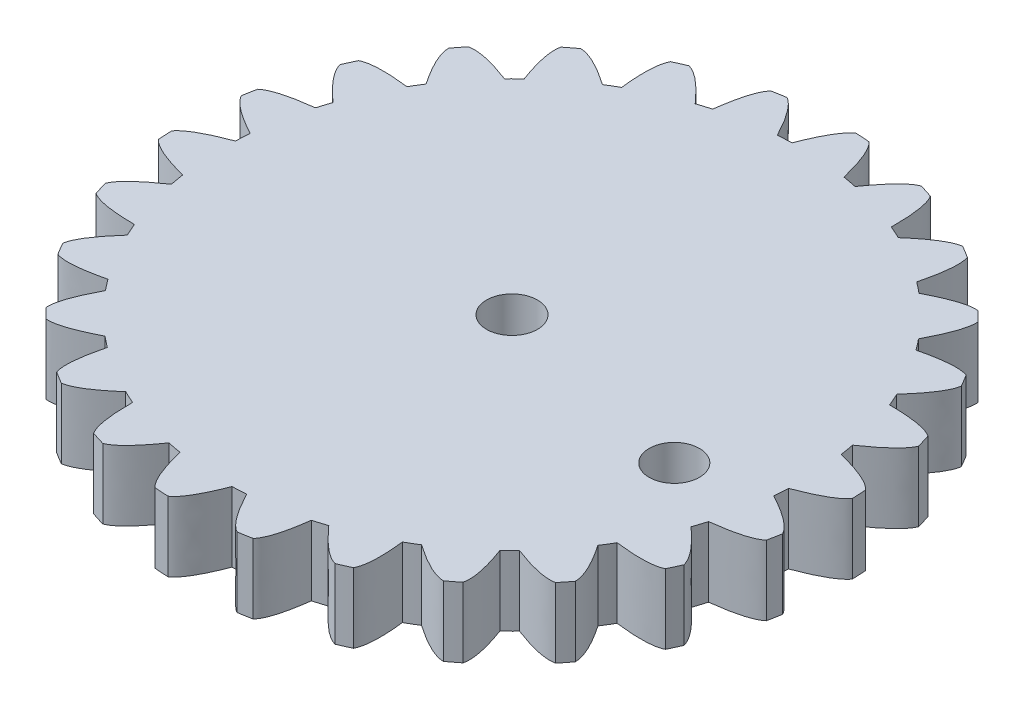
SolidWorks part; units mm, degrees
material "ABS"
ref_plane "Front Plane" through (0, 0, 0) normal (0, 0, 1) x (1, 0, 0)
ref_plane "Top Plane" through (0, 0, 0) normal (0, 1, 0) x (1, 0, 0)
ref_plane "Right Plane" through (0, 0, 0) normal (1, 0, 0) x (0, 0, -1)
sketch "Sketch1" plane through (0, 0, 0) normal (0, 1, 0) x (1, 0, 0)
  line L0 (13.2414, 15.898) -> (16.0492, 13.0578) construction
  line L2 (14.6453, 14.4779) -> (16.7788, 16.587) construction
  line L3 (16.7788, 16.587) -> (16.9174, 16.7241)
  circle A0 centre (0, 0) radius 20.6901
  circle A1 centre (0, 0) radius 23.5936
  spline S0 degree 2 poles (16.0492, 13.0578) (19.1896, 18.9703) (13.2414, 15.898) knots 0 0 0 1 1 1
  point P3 (13.2414, 15.898)
  point P4 (16.0492, 13.0578)
  point P6 (16.4235, 16.9389)
  point P12 (12.4579, 16.5192)
  point P14 (16.9174, 16.7241)
  point P15 (17.1265, 16.2277)
  point P16 (8.7458, 18.7508)
  dimension "D1" = 41.3803
  dimension "D4" = 3
  dimension "D5" = 1
  dimension "D2" = 4
  dimension "D3" = 1
extrude "Boss-Extrude4" add sketch "Sketch1" along normal blind 5 contours A0 | A0 S0 A1 region at (15.5616, 0, -15.3838) region at (0, 0, 0)
pattern_circular "CirPattern6" count 26 every 13.846 about axis through (0, 5, 0) along (0, 1, 0) of "Boss-Extrude4"
sketch "Sketch2" plane through (0, 5, 0) normal (0, 1, 0) x (1, 0, 0)
  circle A0 centre (0, 0) radius 1.825
  dimension "D1" = 3.65
extrude "Cut-Extrude2" cut sketch "Sketch2" against normal blind 10 contours A0 region at (0, 5, 0)
sketch "Sketch4" plane through (0, 0, 0) normal (0, -1, 0) x (1, 0, 0)
  circle A0 centre (15, 3.3804) radius 1.8
  circle A1 centre (0, 0) radius 1.825 construction
  dimension "D1" = 15
  dimension "D2" = 3.6
extrude "Cut-Extrude3" cut sketch "Sketch4" against normal blind 10
equation "\"number-of-teeth\"= 26"
equation "\"gear-size\"= 4mm"
equation "\"circumference\"= \"number-of-teeth\" * ( ( 1 + \"space-between-teeth\" ) * \"gear-size\" )"
equation "\"space-between-teeth\"= .25"
equation "\"D1@Sketch1\" = \"circumference\" / pi"
equation "\"D2@Sketch1\"=\"gear-size\""
equation "\"gear-length\"= 3mm"
equation "\"D4@Sketch1\"=\"gear-length\""
equation "\"D5@Sketch1\"=\"gear-size\" * \"space-between-teeth\""
equation "\"D3@Sketch1\"=\"gear-size\" * \"space-between-teeth\""
equation "\"D1@CirPattern6\"=\"number-of-teeth\""
equation "\"D2@CirPattern6\"=360 / \"number-of-teeth\""
